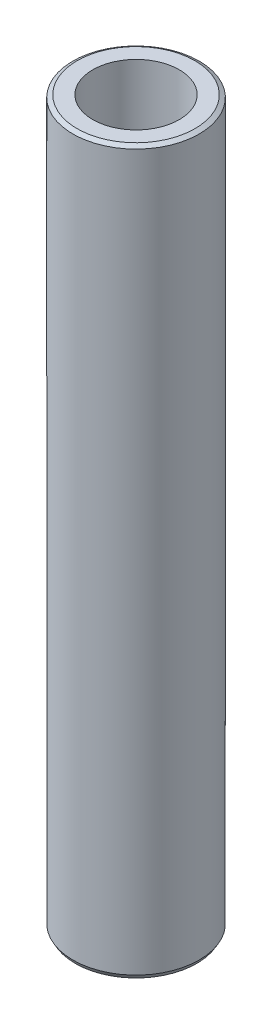
SolidWorks part; units mm, degrees
ref_plane "Front Plane" through (0, 0, 0) normal (0, 0, 1) x (1, 0, 0)
ref_plane "Top Plane" through (0, 0, 0) normal (0, 1, 0) x (1, 0, 0)
ref_plane "Right Plane" through (0, 0, 0) normal (1, 0, 0) x (0, 0, -1)
sketch "Sketch1" plane through (0, 0, 0) normal (0, 1, 0) x (1, 0, 0)
  circle A0 centre (0, 0) radius 52.5
  dimension "SHAFT_OD" = 105
extrude "Boss-Extrude1" add sketch "Sketch1" along normal blind 600
sketch "Sketch2" plane through (0, 0, 0) normal (0, 1, 0) x (1, 0, 0)
  circle A0 centre (0, 0) radius 35.9283
  dimension "BORE_D" = 71.8567
extrude "Cut-Extrude1" cut sketch "Sketch2" along normal through all
chamfer "Chamfer1" distance 2.0525 angle 60 2 edges at (0, 600, 52.5) (0, 0, 52.5) first distance on face at (0, 600, 52.5) first distance on face at (0, 0, 35.9283)
